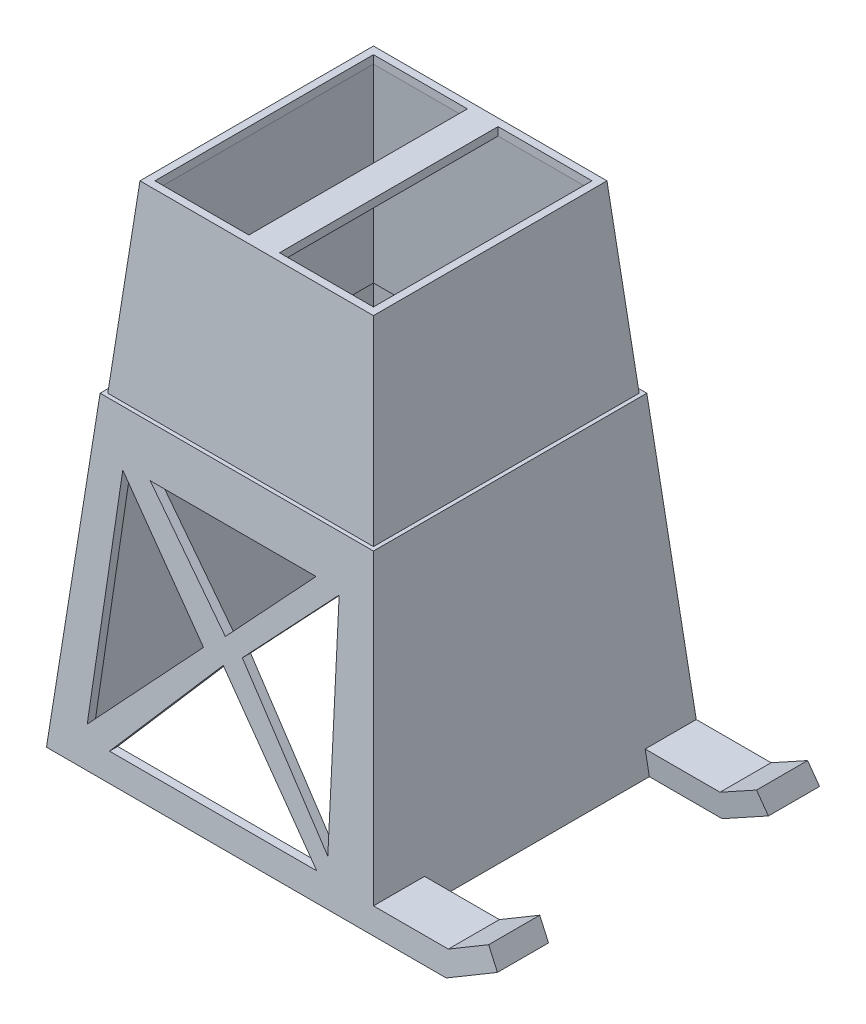
SolidWorks part; units mm, degrees
ref_plane "Front Plane" through (0, 0, 0) normal (0, 0, 1) x (1, 0, 0)
ref_plane "Top Plane" through (0, 0, 0) normal (0, 1, 0) x (1, 0, 0)
ref_plane "Right Plane" through (0, 0, 0) normal (1, 0, 0) x (0, 0, -1)
sketch "Sketch1" plane through (0, 0, 0) normal (0, 1, 0) x (1, 0, 0)
  line L13 (0, 0) -> (-32, 0)
  line L14 (0, 0) -> (0, 32)
  line L15 (0, 32) -> (-32, 32)
  line L16 (-32, 0) -> (-32, 32)
  dimension "D1" = 32
  dimension "D2" = 32
extrude "Boss-Extrude1" add sketch "Sketch1" along normal blind 30 draft 5
sketch "Sketch2" plane through (0, 30, 0) normal (0, 1, 0) x (1, 0, 0)
  line L0 (-29.3753, 2.6247) -> (-2.6247, 2.6247) construction
  line L1 (-29, 29) -> (-3, 29)
  line L2 (-29, 29) -> (-29, 3)
  line L3 (-29, 3) -> (-3, 3)
  line L4 (-3, 29) -> (-3, 3)
  line L5 (-2.6247, 2.6247) -> (-2.6247, 29.3753) construction
  point P5 (-16, 3)
  point P8 (-16, 2.6247)
  point P9 (-3, 16)
  point P12 (-2.6247, 16)
  dimension "D1" = 26
  dimension "D2" = 26
extrude "Boss-Extrude2" add sketch "Sketch2" along normal blind 18 draft 5
shell "Shell1" thickness 0.8 removed face at (-16, 0, -16)
chamfer "Chamfer1" distance 2.5 angle 45 4 edges at (-16, 29.2, -3.3577) (-28.6423, 29.2, -16) (-16, 29.2, -28.6423) (-3.3577, 29.2, -16) first distance on face at (-16, 29.2, -16)
sketch "Sketch3" plane through (0, 47.2, 0) normal (0, -1, 0) x (1, 0, 0)
  line L0 (-5.3079, -26.6921) -> (-26.6921, -26.6921) construction
  line L1 (-17.5, -5.3079) -> (-14.5, -5.3079)
  line L2 (-17.5, -5.3079) -> (-17.5, -26.6921)
  line L3 (-17.5, -26.6921) -> (-14.5, -26.6921)
  line L4 (-14.5, -5.3079) -> (-14.5, -26.6921)
  line L5 (-26.6921, -5.3079) -> (-5.3079, -5.3079) construction
  line L7 (-17.5, -5.3079) -> (-26.6921, -5.3079)
  line L8 (-17.5, -5.3079) -> (-17.5, -26.6921)
  line L9 (-17.5, -26.6921) -> (-26.6921, -26.6921)
  line L10 (-26.6921, -5.3079) -> (-26.6921, -26.6921)
  line L11 (-14.5, -5.3079) -> (-5.3079, -5.3079)
  line L12 (-14.5, -5.3079) -> (-14.5, -26.6921)
  line L13 (-14.5, -26.6921) -> (-5.3079, -26.6921)
  line L14 (-5.3079, -5.3079) -> (-5.3079, -26.6921)
  point P6 (-16, -5.3079)
  point P9 (-16, -5.3079)
  line M13 (-26.6921, -5.3079) -> (-26.6921, -26.6921)
  line M14 (-26.6921, -26.6921) -> (-5.3079, -26.6921)
  line M15 (-5.3079, -26.6921) -> (-5.3079, -5.3079)
  line M16 (-5.3079, -5.3079) -> (-26.6921, -5.3079)
  dimension "D1" = 3
extrude "Cut-Extrude1" cut sketch "Sketch3" against normal through all contours L2 M16 M13 M14 | L4 M16 M14 M15 region at (-22.0961, 47.2, -16) region at (-9.9039, 47.2, -16)
sketch "Sketch4" plane through (0, 0, 0) normal (0, 0, 1) x (1, 0, 0)
  line L0 (-24.0703, 25.4349) -> (-7.8403, 25.4349)
  line L1 (-7.8403, 25.4349) -> (-15.9553, 16.6735)
  line L2 (-15.9553, 16.6735) -> (-24.0703, 25.4349)
  line L3 (-26.7216, 25.0275) -> (-17.9318, 14.8429)
  line L4 (-17.9318, 14.8429) -> (-28.3299, 3.6289)
  line L5 (-28.3299, 3.6289) -> (-26.7216, 25.0275)
  line L6 (-5.5464, 25.0275) -> (-4.8316, 4.165)
  line L7 (-4.8316, 4.165) -> (-14.2131, 15.7801)
  line L8 (-14.2131, 15.7801) -> (-5.5464, 25.0275)
  line L9 (-15.9553, 14.3282) -> (-5.7717, 2.5287)
  line L10 (-5.7717, 2.5287) -> (-26.0515, 2.5287)
  line L11 (-26.0515, 2.5287) -> (-15.9553, 14.3282)
extrude "Cut-Extrude2" cut sketch "Sketch4" against normal through all both and the other way through all
sketch "Sketch5" plane through (0, 0, 0) normal (0, 0, 1) x (1, 0, 0)
  line L0 (0, 0) -> (7.1194, 0)
  line L1 (7.1194, 0) -> (11.8922, 2.7388)
  line L2 (11.8922, 2.7388) -> (10.8785, 4.5052)
  line L3 (10.8785, 4.5052) -> (7.1194, 2.3481)
  line L4 (7.1194, 2.3481) -> (-0.2054, 2.3481)
  line L5 (-2.6247, 30) -> (0, 0) construction
  line L6 (-0.2054, 2.3481) -> (0, 0)
extrude "Boss-Extrude3" add sketch "Sketch5" against normal blind 5 from surface starting at face at (-24.3278, 14.4998, -1.2686)
extrude "Boss-Extrude4" add sketch "Sketch5<2>" along normal blind 5 from surface starting at face at (-24.3278, 14.4998, -30.7314)
sketch "Sketch5<2>" plane through (0, 0, 0) normal (0, 0, 1) x (1, 0, 0) same geometry as "Sketch5"
equation "\"D2@Sketch1\"=\"D1@Sketch1\""
equation "\"D2@Sketch2\"=\"D1@Sketch2\""
